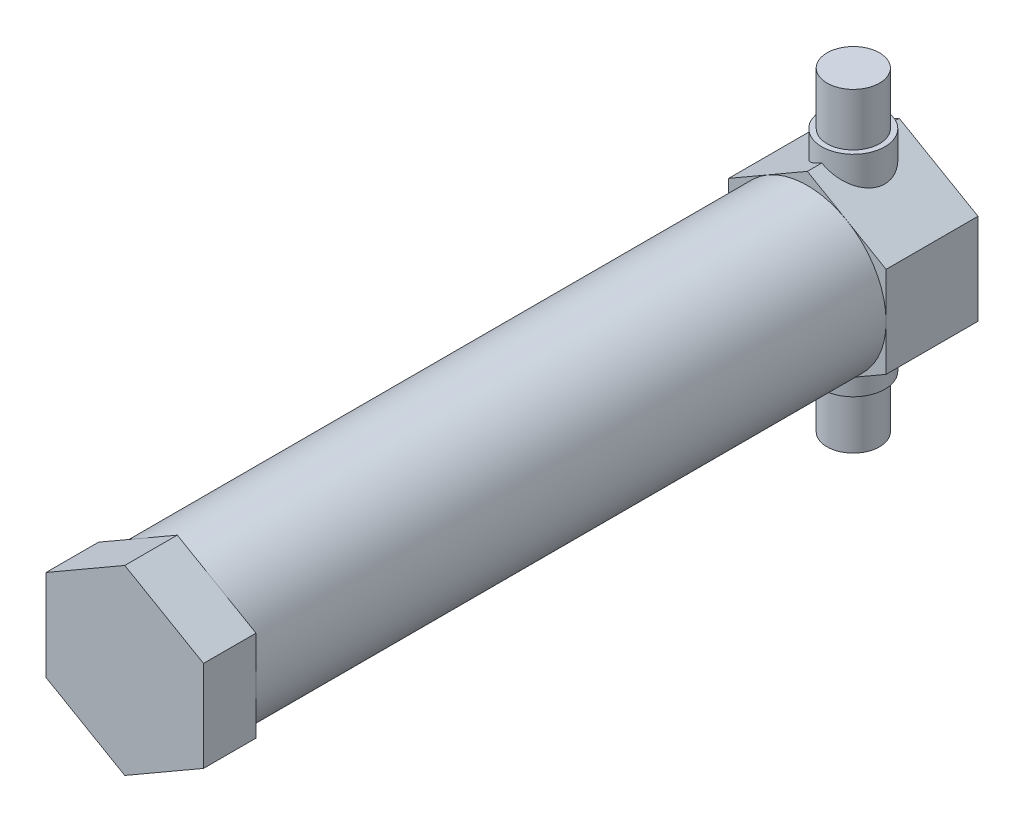
SolidWorks part; units mm, degrees
ref_plane "Front Plane" through (0, 0, 0) normal (0, 0, 1) x (1, 0, 0)
ref_plane "Top Plane" through (0, 0, 0) normal (0, 1, 0) x (1, 0, 0)
ref_plane "Right Plane" through (0, 0, 0) normal (1, 0, 0) x (0, 0, -1)
sketch "Sketch6" plane through (0, 0, 0) normal (0, 0, 1) x (1, 0, 0)
  circle A0 centre (0, 0) radius 9.525
  dimension "D1" = 19.05
extrude "Boss-Extrude5" add sketch "Sketch6" along normal blind 93.6625
sketch "Sketch7" plane through (0, 0, 93.6625) normal (0, 0, 1) x (1, 0, 0)
  line L1 (0, 10.9985) -> (-9.525, 5.4993)
  line L2 (-9.525, 5.4993) -> (-9.525, -5.4993)
  line L3 (-9.525, -5.4993) -> (0, -10.9985)
  line L4 (0, -10.9985) -> (9.525, -5.4993)
  line L5 (9.525, -5.4993) -> (9.525, 5.4993)
  line L6 (9.525, 5.4993) -> (0, 10.9985)
  circle A0 centre (0, 0) radius 9.525 construction
  circle A1 centre (0, 0) radius 9.525 construction
extrude "Boss-Extrude6" add sketch "Sketch7" against normal blind 6.35 contours L6 L1 L2 L3 L4 L5
sketch "Sketch8" plane through (0, 0, 0) normal (0, 0, -1) x (-1, 0, 0)
  line L0 (0, 10.9985) -> (4.7625, 8.2489) construction
  line L1 (0, 10.9985) -> (-9.525, 5.4993)
  line L2 (-9.525, 5.4993) -> (-9.525, -5.4993)
  line L3 (-9.525, -5.4993) -> (0, -10.9985)
  line L4 (0, -10.9985) -> (9.525, -5.4993)
  line L5 (9.525, -5.4993) -> (9.525, 5.4993)
  line L6 (9.525, 5.4993) -> (0, 10.9985)
  circle A0 centre (0, 0) radius 9.525 construction
extrude "Boss-Extrude7" add sketch "Sketch8" against normal blind 11.1125 contours L1 L2 L3 L4 L5 L6
sketch "Sketch9" plane through (0, 0, 0) normal (0, 1, 0) x (1, 0, 0)
  line L0 (0, -11.1125) -> (0, 0) construction
  circle A0 centre (0, -5.5562) radius 3.175
  dimension "D1" = 6.35
extrude "Boss-Extrude8" add sketch "Sketch9" along normal mid plane 38.1
sketch "Sketch11" plane through (0, 0, 0) normal (0, 1, 0) x (1, 0, 0)
  circle A0 centre (0, -5.5562) radius 3.81
  dimension "D1" = 7.62
extrude "Boss-Extrude9" add sketch "Sketch11" along normal mid plane 25.4
sketch "Sketch12" plane through (0, 0, 0) normal (0, 0, -1) x (-1, 0, 0)
  circle A0 centre (0, 0) radius 6.35
  dimension "D1" = 12.7
extrude "Cut-Extrude2" cut sketch "Sketch12" against normal blind 50.8
